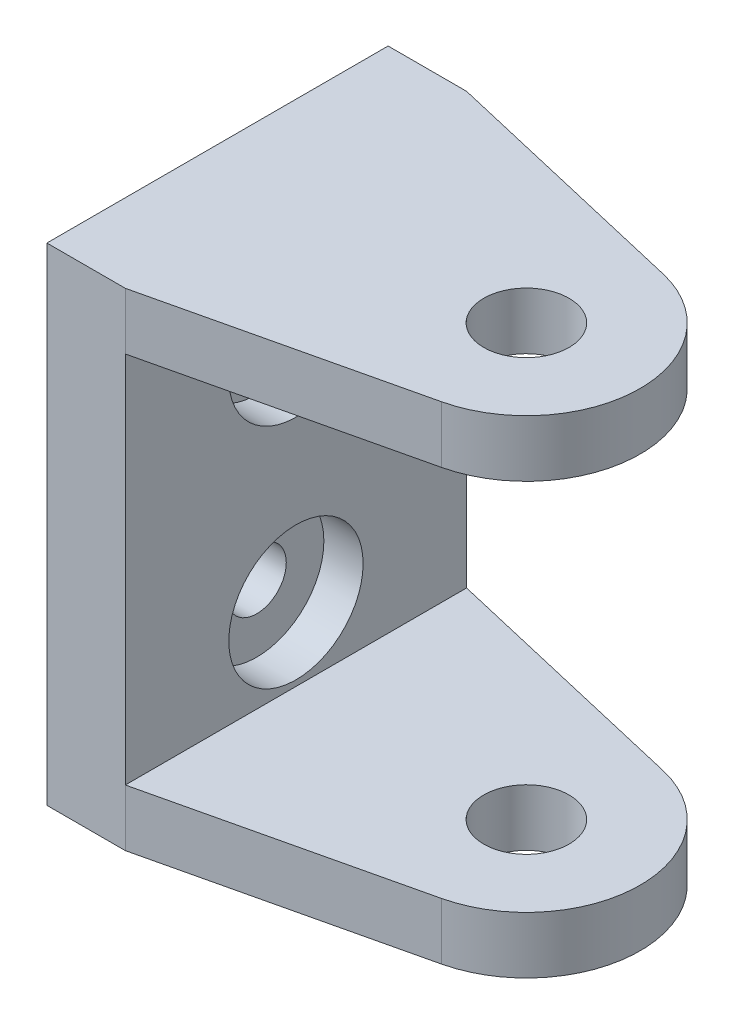
SolidWorks part; units mm, degrees
material "6061-T6 (SS)"
ref_plane "X-Y Datum" through (0, 0, 0) normal (0, 0, 1) x (1, 0, 0)
ref_plane "X-Z Datum" through (0, 0, 0) normal (0, 1, 0) x (1, 0, 0)
ref_plane "Y-Z Datum" through (0, 0, 0) normal (1, 0, 0) x (0, 0, -1)
sketch "Sketch1" plane through (0, 0, 0) normal (0, 1, 0) x (1, 0, 0)
  line L0 (15.6309, -65.821) -> (15.6309, -27.721)
  line L8 (24.3909, -65.821) -> (15.6309, -65.821)
  line L10 (15.6309, -27.721) -> (24.3909, -27.721)
  line L11 (24.3909, -27.721) -> (24.3909, -65.821)
  line L14 (4.2013, -50.8022) -> (13.7532, -50.8022) construction
  line L15 (13.2267, -42.8022) -> (6.1059, -42.8022) construction
  line L16 (4.2013, -46.771) -> (13.2267, -46.771) construction
  point P14 (0, 0)
  dimension "D1" = 38.1
  dimension "D2" = 3.9688
  dimension "D3" = 19.05
  dimension "D4" = 8.76
extrude "Boss-Extrude1" add sketch "Sketch1" along normal blind 54.3789
sketch "Sketch3" plane through (15.6309, 0, 0) normal (-1, 0, 0) x (0, 0, 1)
  line L0 (27.721, 0) -> (65.821, 0) construction
  line L1 (65.821, 54.3789) -> (65.821, 0) construction
  point P0 (46.771, 39.8894)
  point P1 (46.771, 14.4894)
  dimension "D1" = 25.4
  dimension "D2" = 14.4894
  dimension "D3" = 19.05
hole_wizard "CBORE for M6 Hex Head Bolt1" positions "Sketch4" profile "Sketch5" counterbore size "M6" standard "ANSI Metric"
sketch "Sketch4" plane through (24.3909, 0, 0) normal (1, 0, 0) x (0, 0, -1)
  point P0 (-46.771, 14.4894)
  point P3 (-46.771, 39.8894)
sketch "Sketch5" plane through (24.3909, 14.4894, 46.771) normal (0, 1, 0) x (0, 0, -1)
  line L0 (0, 0) -> (0, 16.002)
  line L1 (0, 16.002) -> (3.3, 14.0192)
  line L2 (3.3, 14.0192) -> (3.3, 4.38)
  line L3 (3.3, 4.38) -> (7.5, 4.38)
  line L4 (7.5, 4.38) -> (7.5, 0)
  line L5 (7.5, 0) -> (0, 0)
  line L10 (0, 16.002) -> (-3.3, 14.0192) construction
  line L11 (0, -6.35) -> (0, 107.95) construction
  dimension "Hole Dia." = 6.6
  dimension "Hole Depth" = 16.002
  dimension "C'Bore Dia." = 15
  dimension "C'Bore Depth" = 4.38
  dimension "Drill Angle" = 118
sketch "Sketch6" plane through (0, 54.3789, 0) normal (0, 1, 0) x (1, 0, 0)
  line L2 (24.3909, -27.721) -> (24.3909, -65.821)
  line L3 (24.3909, -65.821) -> (53.0097, -59.1383)
  line L4 (24.3909, -27.721) -> (53.0097, -34.4036)
  circle A2 centre (50.1219, -46.771) radius 4.7625
  arc A3 (53.0097, -59.1383) -> (53.0097, -34.4036) centre (50.1219, -46.771) ccw
  point P3 (50.1219, -46.771)
  dimension "D1" = 9.525
  dimension "D2" = 25.4
extrude "Boss-Extrude2" add sketch "Sketch6" against normal blind 6.35
ref_plane "Plane1" through (0, 27.1894, 0) normal (0, 1, 0) x (1, 0, 0)
mirror "Mirror1" about plane through (0, 27.1894, 0) normal (0, 1, 0) of "Boss-Extrude2"
